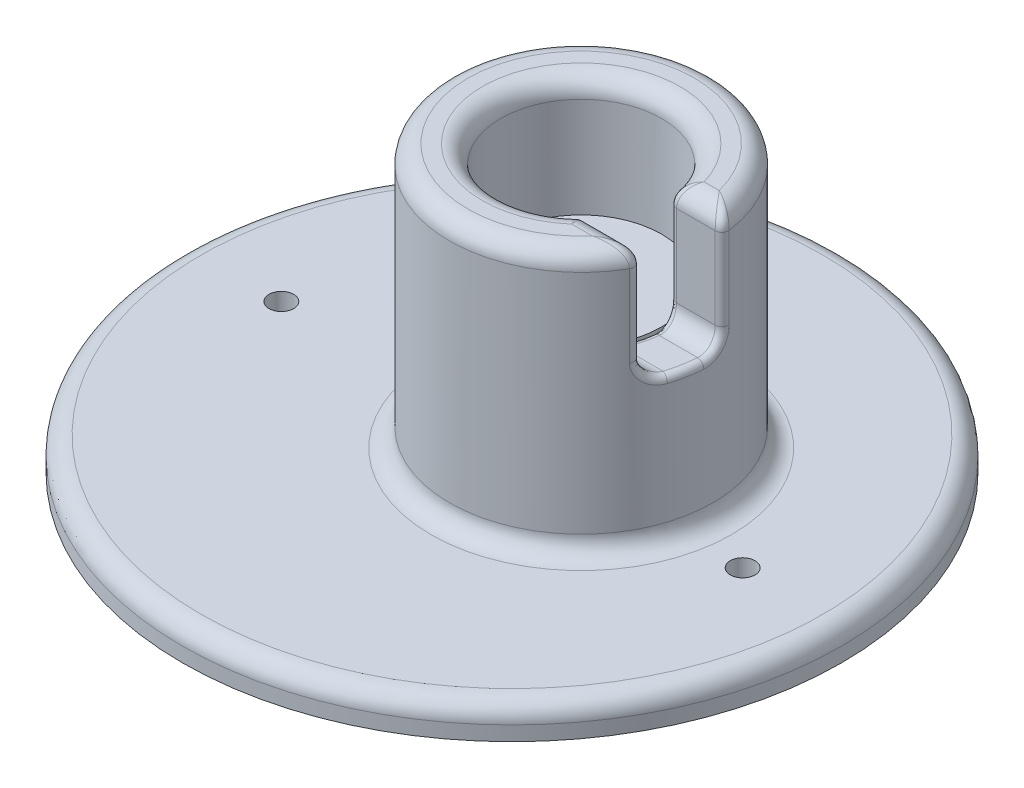
SolidWorks part; units mm, degrees
ref_plane "Front Plane" through (0, 0, 0) normal (0, 0, 1) x (1, 0, 0)
ref_plane "Top Plane" through (0, 0, 0) normal (0, 1, 0) x (1, 0, 0)
ref_plane "Right Plane" through (0, 0, 0) normal (1, 0, 0) x (0, 0, -1)
sketch "Sketch1" plane through (0, 0, 0) normal (0, 1, 0) x (1, 0, 0)
  circle A0 centre (0, 0) radius 7.62
  circle A1 centre (0, 0) radius 63.5
  dimension "D1" = 127
  dimension "D2" = 15.24
extrude "Boss-Extrude1" add sketch "Sketch1" along normal blind 6.35
sketch "Sketch2" plane through (0, 6.35, 0) normal (0, 1, 0) x (1, 0, 0)
  line L0 (9, 11.3527) -> (9, -3.5148) construction
  line L1 (8.89, 4.445) -> (9, 4.445) construction
  circle A0 centre (8.89, 4.445) radius 25.4
  circle A3 centre (8.89, 4.445) radius 15.494
  point P5 (9, 4.445)
  point P8 (0, 0)
  point P9 (0, 0)
  dimension "D1" = 50.8
  dimension "D2" = 4.445
  dimension "D3" = 30.988
  dimension "D4" = 9
extrude "Boss-Extrude2" add sketch "Sketch2" along normal blind 50.8
sketch "Sketch3" plane through (0, 57.15, 0) normal (0, 1, 0) x (1, 0, 0)
  line L8 (43.18, 6.35) -> (43.18, -6.35)
  line L9 (-1.27, 6.35) -> (43.18, 6.35)
  line L13 (-1.27, 6.35) -> (-1.27, -6.35)
  line L14 (-1.27, -6.35) -> (43.18, -6.35)
  circle A0 centre (0, 0) radius 7.62 construction
  dimension "D5" = 6.35
  dimension "D1" = 1.27
  dimension "D2" = 12.7
  dimension "D3" = 44.45
extrude "Cut-Extrude1" cut sketch "Sketch3" against normal blind 22.86
sketch "Sketch4" plane through (0, 6.35, 0) normal (0, 1, 0) x (1, 0, 0)
  circle A0 centre (44.45, 0) radius 2.3812
  circle A1 centre (-44.45, 0) radius 2.3812
  dimension "D1" = 4.7625
  dimension "D2" = 4.7625
  dimension "D3" = 44.45
  dimension "D4" = 44.45
extrude "Cut-Extrude2" cut sketch "Sketch4" against normal through all
fillet "Fillet1" radius 3.556 8 edges at (-16.0907, 57.15, -9.041) (29.2425, 57.15, -6.35) (-5.7989, 57.15, -9.3744) (25.9432, 57.15, 6.35) (25.9432, 34.29, 6.35) (29.2425, 34.29, -6.35) (8.89, 6.35, 20.955) (0, 6.35, 63.5)
fillet "Fillet2" radius 1.27 1 edges at (22.7483, 6.35, -11.3741)
fillet "Fillet3" radius 1.27 14 edges at (20.4615, 36.0424, 5.8587) (20.2892, 55.6882, 7.032) (30.8341, 55.6441, 7.0004) (24.7056, 55.419, -6.8541) (24.3749, 35.0379, -4.9757) (33.7516, 55.2873, -6.779) (20.0045, 45.72, 6.35) (31.8819, 45.72, 6.35) (24.2664, 45.72, -6.35) (34.2185, 45.72, -6.35) (23.7082, 34.29, 0.0812) (32.4276, 35.1407, 5.1019) (33.893, 34.29, 0.028) (34.2649, 35.6273, -5.573)
sketch "Sketch5" plane through (0, 6.35, 0) normal (0, 1, 0) x (1, 0, 0)
  circle A0 centre (8.89, 4.445) radius 15.494
extrude "Boss-Extrude3" add sketch "Sketch5" along normal blind 27.94
sketch "Sketch6" plane through (0, 0, 0) normal (0, -1, 0) x (1, 0, 0)
  circle A0 centre (0, 0) radius 7.62
extrude "Cut-Extrude3" cut sketch "Sketch6" against normal blind 12.7
